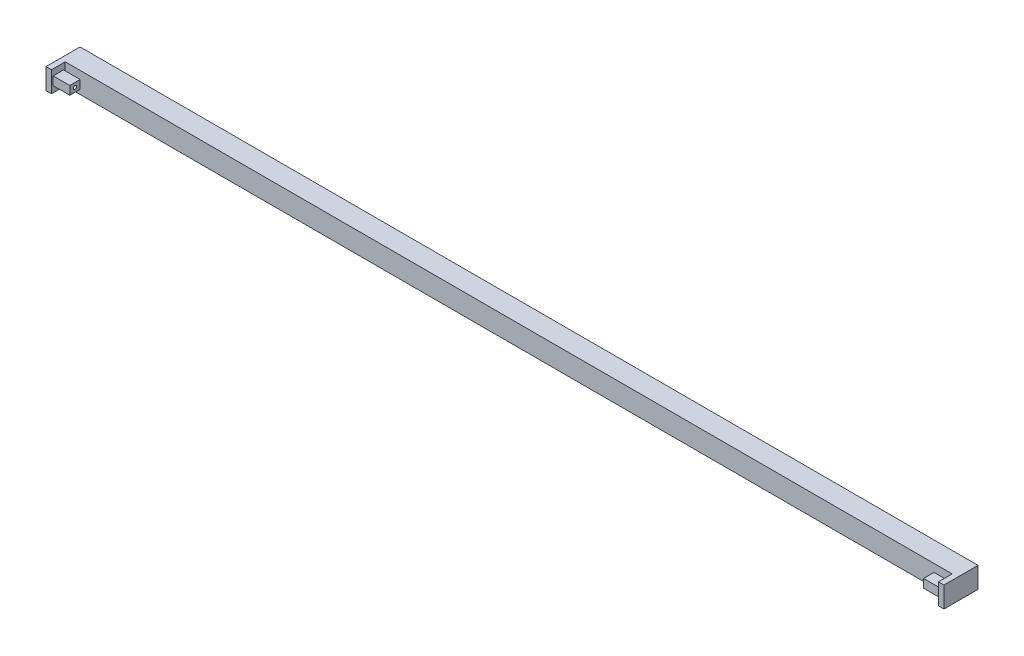
SolidWorks part; units mm, degrees
material "1060 Alloy"
ref_plane "Front Plane" through (0, 0, 0) normal (0, 0, 1) x (1, 0, 0)
ref_plane "Top Plane" through (0, 0, 0) normal (0, 1, 0) x (1, 0, 0)
ref_plane "Right Plane" through (0, 0, 0) normal (1, 0, 0) x (0, 0, -1)
sketch "Sketch1" plane through (0, 0, 0) normal (0, 0, 1) x (1, 0, 0)
  line L1 (0, 0) -> (1635, 0)
  line L2 (0, 0) -> (0, 38)
  line L3 (0, 38) -> (1635, 38)
  line L4 (1635, 0) -> (1635, 38)
  dimension "D1" = 38
  dimension "D2" = 1635
extrude "Boss-Extrude1" add sketch "Sketch1" along normal blind 62
sketch "Sketch2" plane through (0, 0, 62) normal (0, 0, 1) x (1, 0, 0)
  line L0 (1635, 38) -> (0, 38) construction
  line L1 (10, 38) -> (1625, 38)
  line L2 (10, 38) -> (10, 0)
  line L3 (10, 0) -> (1625, 0)
  line L4 (1625, 38) -> (1625, 0)
  line L5 (0, 0) -> (1635, 0) construction
  line L6 (1635, 0) -> (1635, 38) construction
  line L7 (0, 38) -> (0, 0) construction
  dimension "D1" = 10
  dimension "D2" = 10
extrude "Cut-Extrude1" cut sketch "Sketch2" against normal blind 25
sketch "Sketch3" plane through (10, 0, 0) normal (1, 0, 0) x (0, 0, -1)
  line L1 (-40.104, 26.745) -> (-58.9, 26.745)
  line L2 (-40.104, 26.745) -> (-40.104, 11.251)
  line L3 (-40.104, 11.251) -> (-58.9, 11.251)
  line L4 (-58.9, 26.745) -> (-58.9, 11.251)
  line L5 (-37, 38) -> (-62, 38) construction
  line L6 (-62, 38) -> (-62, 0) construction
  dimension "D1" = 18.796
  dimension "D2" = 15.494
  dimension "D3" = 11.255
  dimension "D4" = 3.1
extrude "Boss-Extrude2" add sketch "Sketch3" along normal blind 30.226
sketch "Sketch5" plane through (1625, 0, 0) normal (-1, 0, 0) x (0, 0, 1)
  line L0 (58.9, 26.74) -> (39.9812, 26.74)
  line L1 (58.9, 26.74) -> (58.9, 11.246)
  line L2 (58.9, 11.246) -> (39.9812, 11.246)
  line L3 (39.9812, 26.74) -> (39.9812, 11.246)
  line L4 (37, 38) -> (62, 38) construction
  line L5 (62, 0) -> (62, 38) construction
  dimension "D1" = 11.26
  dimension "D2" = 3.1
extrude "Boss-Extrude3" add sketch "Sketch5" along normal blind 30.226
sketch "Sketch6" plane through (40.226, 0, 0) normal (1, 0, 0) x (0, 0, -1)
  line L0 (-40.104, 11.251) -> (-40.104, 26.745) construction
  line L1 (-58.9, 26.745) -> (-58.9, 11.251) construction
  line L3 (-58.9, 11.251) -> (-40.104, 11.251) construction
  circle A0 centre (-49.504, 18.996) radius 3
  dimension "D1" = 9.4
  dimension "D2" = 9.396
  dimension "D3" = 7.745
extrude "Cut-Extrude2" cut sketch "Sketch6" against normal blind 10
sketch "Sketch7" plane through (1594.774, 0, 0) normal (-1, 0, 0) x (0, 0, 1)
  line L0 (58.9, 26.74) -> (39.9812, 26.74) construction
  line L1 (39.9812, 26.74) -> (39.9812, 11.246) construction
  circle A0 centre (49.3812, 18.995) radius 3
  dimension "D1" = 7.745
  dimension "D2" = 9.4
extrude "Cut-Extrude3" cut sketch "Sketch7" against normal blind 10
